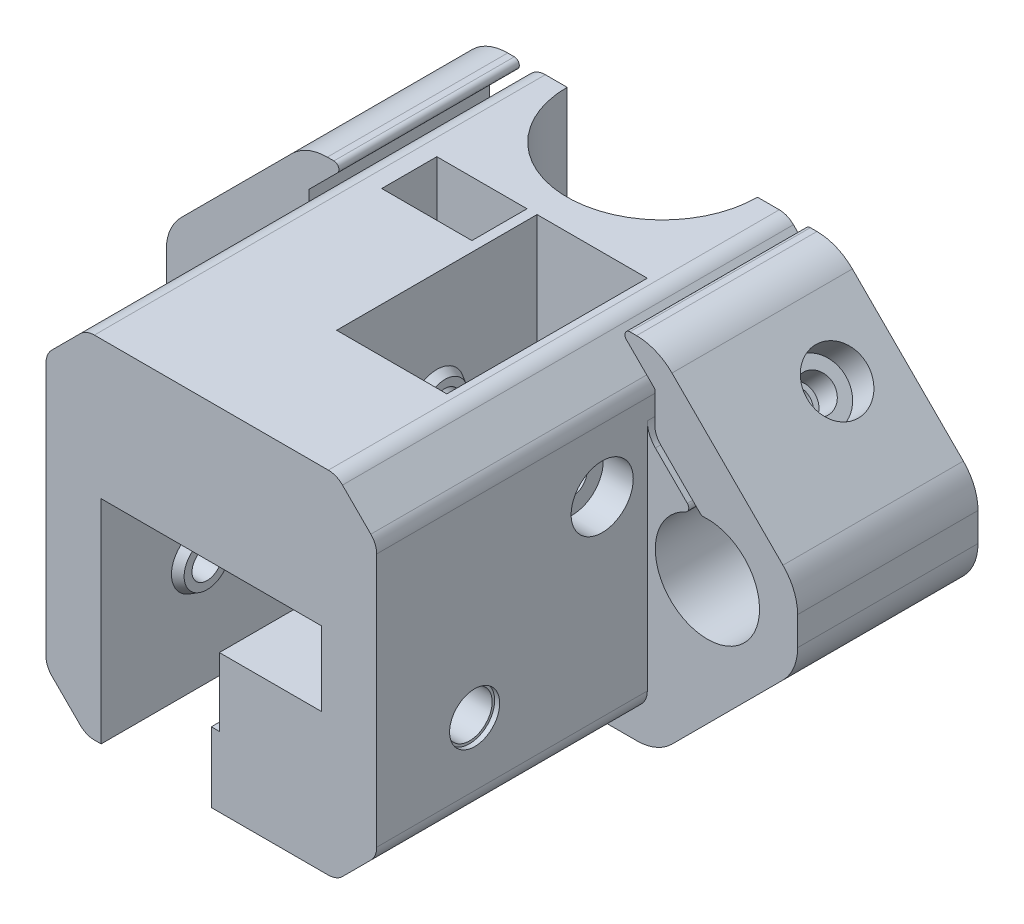
SolidWorks part; units mm, degrees
ref_plane "XY" through (0, 0, 0) normal (0, 0, 1) x (1, 0, 0)
ref_plane "XZ" through (0, 0, 0) normal (0, 1, 0) x (1, 0, 0)
ref_plane "YZ" through (0, 0, 0) normal (1, 0, 0) x (0, 0, -1)
sketch "Sketch1" plane through (0, 0, 0) normal (0, 0, 1) x (1, 0, 0)
  line L0 (-17.5, 17.5) -> (-31.5, 3.5)
  line L1 (31.5, -17.5) -> (17.5, -17.5) construction
  line L2 (31.5, -17.5) -> (31.5, -3.5) construction
  line L3 (31.5, 17.5) -> (17.5, 17.5) construction
  line L4 (-31.5, -17.5) -> (-31.5, -3.5) construction
  line L5 (31.5, -17.5) -> (-31.5, 17.5) construction
  line L6 (31.5, 17.5) -> (-31.5, -17.5) construction
  line L7 (-12.5, 17.5) -> (-16.5, 13.5)
  line L8 (-16.5, 13.5) -> (-16.5, 9.535)
  line L9 (-16.5, 9.535) -> (-21.0432, 4.9918)
  line L10 (-13.5607, 17.5) -> (-17.25, 13.8107)
  line L11 (-17.25, 13.8107) -> (-17.25, 9.8457)
  line L12 (-17.25, 9.8457) -> (-21.9273, 5.1684)
  line L13 (-17.25, 9.8457) -> (-21.5736, 5.5221) construction
  line L14 (-13.0303, 18.0303) -> (-17.25, 13.8107) construction
  line L15 (-13.5607, 17.5) -> (-17.5, 17.5)
  line L16 (0, 0) -> (-59.6161, 0) construction
  line L17 (0, 0) -> (0, 36.6742) construction
  line L18 (-17.5, -17.5) -> (-31.5, -3.5)
  line L19 (17.5, -17.5) -> (31.5, -3.5)
  line L20 (16.5, 9.535) -> (21.0432, 4.9918)
  line L21 (16.5, 13.5) -> (16.5, 9.535)
  line L22 (12.5, 17.5) -> (16.5, 13.5)
  line L23 (13.5607, 17.5) -> (17.25, 13.8107)
  line L24 (17.25, 13.8107) -> (17.25, 9.8457)
  line L25 (17.25, 9.8457) -> (21.9273, 5.1684)
  line L26 (17.5, 17.5) -> (31.5, 3.5)
  line L27 (12.5, 17.5) -> (-12.5, 17.5)
  line L28 (-17.5, 17.5) -> (-31.5, 17.5) construction
  line L29 (-31.5, 3.5) -> (-31.5, 17.5) construction
  line L30 (-31.5, -3.5) -> (-31.5, 3.5)
  line L31 (-17.5, -17.5) -> (-31.5, -17.5) construction
  line L32 (17.5, -17.5) -> (-17.5, -17.5)
  line L33 (31.5, -3.5) -> (31.5, 3.5)
  line L34 (31.5, 3.5) -> (31.5, 17.5) construction
  line L35 (17.5, 17.5) -> (13.5607, 17.5)
  arc A0 (-21.9273, 5.1684) -> (-21.0432, 4.9918) centre (-22.5, 0) ccw
  arc A1 (21.9273, 5.1684) -> (21.0432, 4.9918) centre (22.5, 0) cw
  point P0 (0, 0)
  dimension "D1" = 63
  dimension "D6" = 10.4
  dimension "D2" = 35
  dimension "D3" = 14
  dimension "D4" = 14
  dimension "D5" = 22.5
  dimension "D7" = 19
  dimension "D8" = 15
  dimension "D9" = 9.535
  dimension "D10" = 0.75
extrude "Boss-Extrude1" add sketch "Sketch1" along normal blind 18
sketch "Sketch2" plane through (0, 17.5, 0) normal (0, 1, 0) x (1, 0, 0)
  line L0 (12.5, 0) -> (-12.5, 0) construction
  line L1 (12.5, -18) -> (-12.5, -18) construction
  line L2 (-10, -18) -> (-1, -18)
  line L3 (-10, -18) -> (-10, -12.5)
  line L4 (-10, -12.5) -> (-1, -12.5)
  line L5 (-1, -18) -> (-1, -12.5)
  circle A0 centre (0, 0) radius 9.5
  point P10 (-5.5, -12.5)
  dimension "D1" = 19
  dimension "D2" = 9
  dimension "D3" = 5.5
  dimension "D4" = 5.5
extrude "Cut-Extrude1" cut sketch "Sketch2" against normal through all
fillet "Fillet1" radius 5 8 edges at (17.5, 17.5, 9) (31.5, 3.5, 9) (31.5, -3.5, 9) (17.5, -17.5, 9) (-17.5, -17.5, 9) (-31.5, -3.5, 9) (-31.5, 3.5, 9) (-17.5, 17.5, 9)
fillet "Fillet2" radius 0.5 6 edges at (-21.9273, 5.1684, 9) (-21.0432, 4.9918, 9) (21.0432, 4.9918, 9) (21.9273, 5.1684, 9) (-13.5607, 17.5, 9) (13.5607, 17.5, 9)
fillet "Fillet3" radius 2 2 edges at (17.25, 9.8457, 9) (-17.25, 9.8457, 9)
fillet "Fillet4" radius 2.75 2 edges at (-16.5, 9.535, 9) (16.5, 9.535, 9)
sketch "Sketch3" plane through (-17.5, 17.5, 0) normal (-0.7071, 0.7071, 0) x (0, 0, 1)
  line L0 (0, -2.0711) -> (0, -17.7279) construction
  circle A0 centre (6, -8.4) radius 1.75
  dimension "D1" = 3.5
  dimension "D2" = 6
  dimension "D3" = 8.4
ref_plane "Plane1" through (0, 0, 6) normal (0, 0, -1) x (-1, 0, 0)
sketch "Sketch4" plane through (0, 0, 6) normal (0, 0, -1) x (-1, 0, 0)
  line L0 (23.4397, 11.5603) -> (11.3618, -0.5176) construction
  line L1 (24.6771, 10.3229) -> (22.2023, 12.7977) construction
  line L2 (23.4397, 11.5603) -> (25.561, 9.439)
  line L3 (18.9645, 16.0355) -> (30.0355, 4.9645) construction
  line L4 (25.561, 9.439) -> (23.4397, 7.3177)
  line L5 (23.4397, 7.3177) -> (22.5558, 8.2015)
  line L6 (12.8331, 0.9537) -> (23.4397, 11.5603)
  line L9 (22.5558, 8.2015) -> (14.0705, -0.2837)
  line L10 (14.0705, -0.2837) -> (12.8331, 0.9537)
  dimension "D1" = 3
  dimension "D2" = 1.75
  dimension "D3" = 3
  dimension "D4" = 15
revolve "Cut-Revolve1" cut sketch "Sketch4" angle 360 about L0
sketch "Sketch6" plane through (-6.8934, 6.8934, 0) normal (-0.7071, 0.7071, 0) x (0, 0, 1)
  line L0 (0, -2.0711) -> (0, -17.7279) construction
  line L1 (3.425, -9.8867) -> (6, -11.3734)
  line L2 (6, -11.3734) -> (8.575, -9.8867)
  line L3 (8.575, -9.8867) -> (8.575, -6.9133)
  line L4 (8.575, -6.9133) -> (6, -5.4266)
  line L5 (6, -5.4266) -> (3.425, -6.9133)
  line L6 (3.425, -6.9133) -> (3.425, -9.8867)
  circle A0 centre (6, -8.4) radius 2.575 construction
  dimension "D1" = 5.15
extrude "Cut-Extrude2" cut sketch "Sketch6" against normal blind 15
mirror "Mirror1" about plane through (0, 0, 0) normal (1, 0, 0) of "Cut-Extrude2", "Cut-Revolve1"
sketch "Sketch7" plane through (0, 0, 0) normal (0, 0, -1) x (-1, 0, 0)
  circle A0 centre (-12.5, 12.5) radius 1.6
  dimension "D1" = 3.2
  dimension "D2" = 12.5
  dimension "D3" = 12.5
extrude "Cut-Extrude3" cut sketch "Sketch7" against normal blind 10
sketch "Sketch8" plane through (0, 0, 0) normal (0, 0, -1) x (-1, 0, 0)
  circle A0 centre (-12.5, 12.5) radius 2.35
  dimension "D1" = 4.7
extrude "Cut-Extrude4" cut sketch "Sketch8" against normal blind 5
sketch "Sketch9" plane through (0, 0, 0) normal (0, 0, -1) x (-1, 0, 0)
  circle A0 centre (-12.5, 12.5) radius 2.5
  dimension "D1" = 5
extrude "Cut-Extrude5" cut sketch "Sketch9" against normal blind 0.5
mirror "Mirror2" about plane through (0, 0, 0) normal (0, 1, 0) of "Cut-Extrude5", "Cut-Extrude4", "Cut-Extrude3"
mirror "Mirror3" about plane through (0, 0, 0) normal (1, 0, 0) of "Mirror2", "Cut-Extrude5", "Cut-Extrude4", "Cut-Extrude3"
sketch "Sketch10" plane through (0, 0, 18) normal (0, 0, 1) x (1, 0, 0)
  line L0 (12.5, 17.5) -> (-1, 17.5) construction
  line L1 (16.5, 13.5) -> (12.5, 17.5) construction
  line L2 (16.5, 10.6741) -> (16.5, 13.5) construction
  line L3 (12.5, 17.5) -> (-12.5, 17.5)
  line L4 (16.5, 13.5) -> (12.5, 17.5)
  line L5 (16.5, -13.5) -> (16.5, 13.5)
  line L6 (0, -17.5) -> (0, 17.5) construction
  line L7 (0, 0) -> (16.5, 0) construction
  line L8 (-16.5, -13.5) -> (-16.5, 13.5)
  line L9 (-16.5, 13.5) -> (-12.5, 17.5)
  line L10 (-16.5, -13.5) -> (-12.5, -17.5)
  line L11 (16.5, -13.5) -> (12.5, -17.5)
  line L12 (12.5, -17.5) -> (-12.5, -17.5)
  point P14 (-16.5, 0)
extrude "Boss-Extrude2" add sketch "Sketch10" along normal offset from surface (27 mm away) 45 up to face at (-10, -12.5, 0)
sketch "Sketch11" plane through (0, 17.5, 0) normal (0, 1, 0) x (1, 0, 0)
  line L0 (-1, -12.5) -> (-10, -12.5) construction
  line L1 (0, -12.5) -> (11, -12.5)
  line L2 (0, -12.5) -> (0, -32.5)
  line L3 (0, -32.5) -> (11, -32.5)
  line L4 (11, -12.5) -> (11, -32.5)
  dimension "D1" = 20
  dimension "D2" = 11
extrude "Cut-Extrude6" cut sketch "Sketch11" against normal blind 21.2
sketch "Sketch12" plane through (0, 0, 32.5) normal (0, 0, -1) x (-1, 0, 0)
  line L0 (0, -3.7) -> (-11, -3.7) construction
  line L1 (0, -3.7) -> (-11, -3.7)
  line L2 (0, 0) -> (-16.491, 0) construction
  line L3 (-11, -3.7) -> (-11, 3.7)
  line L4 (-11, 3.7) -> (0, 3.7)
  line L5 (0, 3.7) -> (0, -3.7)
  line L6 (0, -3.7) -> (0, -3.5912)
  line M2 (-11, 17.5) -> (-11, -3.7)
  line M3 (-11, -3.7) -> (0, -3.7)
  line M4 (0, -3.7) -> (0, 17.5)
extrude "Cut-Extrude7" cut sketch "Sketch12" against normal up to surface (12.5 mm away) contours L2 L4 M4 M2 | L5 L2 L3 M3 M4 region at (5.5, -1.85, 32.5) region at (5.5, 1.85, 32.5) up to face at (0, 0, 45)
fillet "Fillet5" radius 10 1 edges at (5.5, -3.7, 12.5)
sketch "Sketch13" plane through (0, -17.5, 0) normal (0, -1, 0) x (1, 0, 0)
  line L1 (0, 45) -> (-11, 45)
  line L2 (0, 45) -> (0, 25.2)
  line L3 (0, 25.2) -> (-11, 25.2)
  line L4 (-11, 45) -> (-11, 25.2)
  dimension "D1" = 11
  dimension "D2" = 19.8
extrude "Cut-Extrude8" cut sketch "Sketch13" against normal up to surface (21.2 mm away) up to face at (5.5, 3.7, 38.75)
fillet "Fillet6" radius 10 1 edges at (-5.5, 3.7, 25.2) tangent propagation no
sketch "Sketch14" plane through (0, 0, 45) normal (0, 0, 1) x (1, 0, 0)
  line L0 (-11, 3.7) -> (11, 3.7) construction
  line L1 (11, -3.7) -> (11, 3.7) construction
  line L2 (0, -3.7) -> (11, -3.7) construction
  line L3 (0, 3.7) -> (11, 3.7)
  line L4 (11, -3.7) -> (11, 3.7)
  line L5 (0, -3.7) -> (11, -3.7)
  line L6 (0, -3.7) -> (0, 3.7)
extrude "Cut-Extrude9" cut sketch "Sketch14" against normal up to surface (12.5 mm away) up to face at (5.5, 10.4143, 32.5)
sketch "Sketch15" plane through (-11, 0, 0) normal (1, 0, 0) x (0, 0, -1)
  circle A0 centre (-35.23, -6.365) radius 2.75
  dimension "D1" = 5.5
  dimension "D2" = 35.23
  dimension "D3" = 6.365
extrude "Boss-Extrude3" add sketch "Sketch15" along normal blind 0.8 draft 30
sketch "Sketch16" plane through (0, 0, 0) normal (-1, 0, 0) x (0, 0, 1)
  line L1 (45, -3.7) -> (31, -3.7)
  line L2 (45, -3.7) -> (45, -10.515)
  line L3 (45, -10.515) -> (31, -10.515)
  line L4 (31, -3.7) -> (31, -10.515)
  dimension "D1" = 6.815
  dimension "D2" = 14
extrude "Cut-Extrude10" cut sketch "Sketch16" against normal blind 0.8
ref_plane "Plane2" through (0, 0, 35.23) normal (0, 0, 1) x (1, 0, 0)
sketch "Sketch17" plane through (0, 0, 35.23) normal (0, 0, 1) x (1, 0, 0)
  line L0 (31.9477, -6.365) -> (-32.235, -6.365) construction
  line L2 (-11, -9.115) -> (-11, -3.615) construction
  line L3 (-11, -9.115) -> (-11, -3.615) construction
  line L4 (-16.5, -6.365) -> (-16.5, -3.265)
  line L5 (-16.5, 10.6741) -> (-16.5, -13.5) construction
  line L6 (-16.5, -3.265) -> (-13.5, -3.265)
  line L7 (-13.5, -3.265) -> (-13.5, -4.865)
  line L8 (-13.5, -4.865) -> (11.5, -4.865)
  line L9 (11.5, -4.865) -> (11.5, -4.115)
  line L10 (11.5, -4.115) -> (16, -4.115)
  line L11 (16, -4.115) -> (16, -3.865)
  line L12 (16, -3.865) -> (16.5, -3.865)
  line L13 (16.5, 13.5) -> (16.5, -13.5) construction
  line L14 (16.5, -3.865) -> (16.5, -6.365)
  line L15 (16.5, -13.5) -> (16.5, 10.6741) construction
  line L16 (16.5, -6.365) -> (-16.5, -6.365)
  point P5 (-11, -6.365)
  dimension "D1" = 3
  dimension "D2" = 3.1
  dimension "D3" = 1.5
  dimension "D4" = 2.25
  dimension "D5" = 2.5
  dimension "D6" = 0.5
  dimension "D7" = 5
revolve "Cut-Revolve2" cut sketch "Sketch17" angle 360 about L0
sketch "Sketch18" plane through (11, 0, 0) normal (-1, 0, 0) x (0, 0, 1)
  circle A0 centre (22.5, 6.365) radius 1.5
  dimension "D1" = 6.365
  dimension "D3" = 3
  dimension "D2" = 22.5
sketch "Sketch19" plane through (11, 0, 0) normal (-1, 0, 0) x (0, 0, 1)
  circle A0 centre (22.5, 6.365) radius 2.75
  dimension "D1" = 5.5
extrude "Boss-Extrude4" add sketch "Sketch19" along normal blind 0.8 draft 30
ref_plane "Plane3" through (5.5, 0, 0) normal (1, 0, 0) x (0, 0, -1)
mirror "Mirror4" about plane through (5.5, 0, 0) normal (1, 0, 0) of "Boss-Extrude4"
ref_plane "Plane4" through (0, 0, 22.5) normal (0, 0, 1) x (1, 0, 0)
sketch "Sketch20" plane through (0, 0, 22.5) normal (0, 0, 1) x (1, 0, 0)
  line L0 (11, 6.365) -> (-21.7769, 6.365) construction
  line L1 (16.5, 6.365) -> (16.5, 9.465)
  line L2 (16.5, 13.5) -> (16.5, -13.5) construction
  line L3 (16.5, 9.465) -> (13.5, 9.465)
  line L4 (13.5, 9.465) -> (13.5, 7.865)
  line L5 (13.5, 7.865) -> (-11.5, 7.865)
  line L6 (-11.5, 7.865) -> (-11.5, 8.615)
  line L7 (-11.5, 8.615) -> (-16, 8.615)
  line L8 (-16, 8.615) -> (-16, 8.865)
  line L9 (-16, 8.865) -> (-16.5, 8.865)
  line L10 (-16.5, -13.5) -> (-16.5, 13.5) construction
  line L11 (-16.5, 8.865) -> (-16.5, 6.365)
  line L12 (-16.5, 10.6741) -> (-16.5, -13.5) construction
  line L13 (-16.5, 6.365) -> (16.5, 6.365)
  dimension "D1" = 3.1
  dimension "D2" = 3
  dimension "D3" = 1.5
  dimension "D4" = 2.25
  dimension "D5" = 2.5
  dimension "D6" = 0.5
  dimension "D7" = 25
revolve "Cut-Revolve3" cut sketch "Sketch20" angle 360 about L0
fillet "Fillet7" radius 2 8 edges at (16.5, -13.5, 31.5) (12.5, -17.5, 31.5) (-12.5, -17.5, 31.5) (-16.5, -13.5, 31.5) (16.5, 13.5, 22.5) (12.5, 17.5, 22.5) (-12.5, 17.5, 22.5) (-16.5, 13.5, 22.5)
